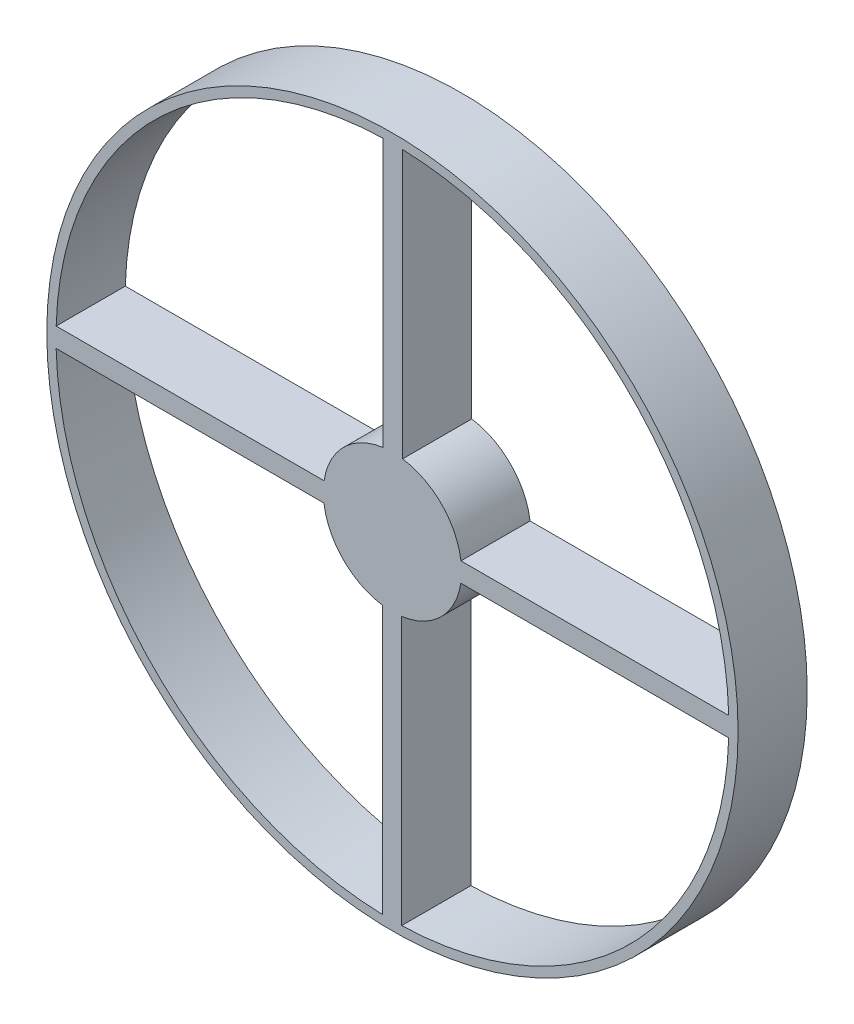
SolidWorks part; units mm, degrees
ref_plane "Front Plane" through (0, 0, 0) normal (0, 0, 1) x (1, 0, 0)
ref_plane "Top Plane" through (0, 0, 0) normal (0, 1, 0) x (1, 0, 0)
ref_plane "Right Plane" through (0, 0, 0) normal (1, 0, 0) x (0, 0, -1)
sketch "Sketch4" plane through (0, 0, 0) normal (0, 0, 1) x (1, 0, 0)
  circle A0 centre (0, 0) radius 75
  dimension "D1" = 150
extrude "Boss-Extrude2" add sketch "Sketch4" along normal blind 15
sketch "Sketch6" plane through (0, 0, 0) normal (0, 0, 1) x (1, 0, 0)
  line L2 (0, 0) -> (0, 73) construction
  line L5 (0, 0) -> (73, 0) construction
  line L6 (0, 15) -> (2.2066, 15) construction
  line L7 (15, 0) -> (14.6783, 3.09) construction
  line L8 (15, 0) -> (15, 2) construction
  line L9 (2.2066, 15) -> (2.2066, 69.7293)
  line L10 (15, 2) -> (72.9726, 2)
  line L11 (2.2066, 69.7293) -> (2.2066, 72.9666)
  line L12 (2.2066, 15) -> (2.2066, 14.8368)
  line L13 (15, 2) -> (14.8661, 2)
  arc A7 (2.2066, 72.9666) -> (72.9726, 2) centre (0, 0) cw
  arc A8 (2.2066, 14.8368) -> (14.8661, 2) centre (0, 0) cw
  dimension "D3" = 2.2066
  dimension "D4" = 2
extrude "Cut-Extrude1" cut sketch "Sketch6" along normal through all both and the other way through all
pattern_circular "CirPattern1" count 4 over 360 about axis through (0, 0, 15) along (0, 0, 1) of "Cut-Extrude1"
shell "Shell1" thickness 2 removed face at (-27.1245, -26.995, 0)
sketch "Sketch7" plane through (0, 0, 13) normal (0, 0, -1) x (-1, 0, 0)
  circle A0 centre (0, 0) radius 12.5033
extrude "Boss-Extrude3" add sketch "Sketch7" along normal blind 12.5
sketch "Sketch8" plane through (0, 0, 0.5) normal (0, 0, -1) x (-1, 0, 0)
  circle A0 centre (0, 0) radius 3.25
  circle A1 centre (0, 0) radius 2.25
  dimension "D1" = 6.5
  dimension "D2" = 4.5
extrude "Boss-Extrude4" add sketch "Sketch8" along normal blind 8.5
sketch "Sketch9" plane through (0, 0, 0.5) normal (0, 0, -1) x (-1, 0, 0)
  circle A0 centre (0, 0) radius 3.25
  circle A1 centre (0, 0) radius 12.5033
extrude "Cut-Extrude2" cut sketch "Sketch9" against normal blind 10
